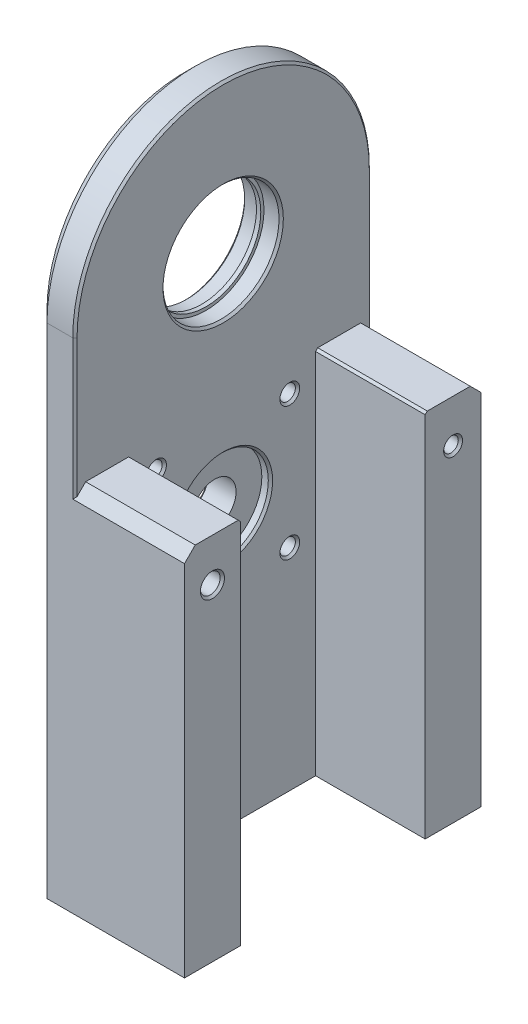
SolidWorks part; units mm, degrees
ref_plane "Ebene vorne" through (0, 0, 0) normal (0, 0, 1) x (1, 0, 0)
ref_plane "Ebene oben" through (0, 0, 0) normal (0, 1, 0) x (1, 0, 0)
ref_plane "Ebene rechts" through (0, 0, 0) normal (1, 0, 0) x (0, 0, -1)
sketch "Sketch2" plane through (0, 0, 0) normal (1, 0, 0) x (0, 0, -1)
  line L1 (0, 0) -> (69, 0)
  line L2 (0, 0) -> (0, 86)
  line L3 (0, 86) -> (69, 86)
  line L4 (69, 0) -> (69, 86)
  line L5 (0, 0) -> (69, 86) construction
  line L6 (0, 86) -> (69, 0) construction
  line L7 (0, 86) -> (69, 86)
  line L8 (0, 86) -> (0, 116)
  line L9 (0, 116) -> (69, 116)
  line L10 (69, 86) -> (69, 116)
  line L11 (0, 86) -> (69, 116) construction
  line L12 (0, 116) -> (69, 86) construction
  circle A0 centre (34.5, 116) radius 34.5
  circle A1 centre (34.5, 116) radius 12.75
  point P4 (34.5, 43)
  point P9 (34.5, 101)
  dimension "D4" = 25.5
  dimension "D1" = 69
  dimension "D2" = 86
  dimension "D3" = 30
extrude "Boss-Extrude1" add sketch "Sketch2" along normal blind 34.5 contours A0 L3 L2 L1 L4 | L7 A0 region at (0, 42.2679, -34.5) region at (0, 84.1895, -34.5)
sketch "Sketch9" plane through (34.5, 0, 0) normal (1, 0, 0) x (0, 0, -1)
  line L0 (13, 86) -> (13, 0)
  line L1 (0, 86) -> (69, 86) construction
  line L2 (0, 0) -> (69, 0) construction
  line L3 (13, 0) -> (56, 0)
  line L4 (56, 0) -> (56, 86)
  line L5 (56, 86) -> (13, 86)
  line L6 (0, 0) -> (0, 86) construction
  line L7 (69, 0) -> (69, 86) construction
  line L9 (13, 0) -> (56, 0)
  line L10 (13, 0) -> (13, 43)
  line L11 (13, 43) -> (56, 43)
  line L12 (56, 0) -> (56, 43)
  line L13 (13, 0) -> (56, 43) construction
  line L14 (13, 43) -> (56, 0) construction
  line L15 (56, 43) -> (13, 43)
  line L16 (56, 43) -> (56, 86)
  line L17 (56, 86) -> (13, 86)
  line L18 (13, 43) -> (13, 86)
  line L19 (56, 43) -> (13, 86) construction
  line L20 (56, 86) -> (13, 43) construction
  circle A0 centre (34.5, 64.5) radius 11
  circle A1 centre (34.5, 64.5) radius 5
  point P15 (34.5, 21.5)
  point P19 (34.5, 64.5)
  line M2 (69, 86) -> (0, 86)
  line M4 (0, 0) -> (69, 0)
  dimension "D3" = 22
  dimension "D4" = 10
  dimension "D1" = 13
  dimension "D2" = 13
extrude "Cut-Extrude1" cut sketch "Sketch9" against normal offset from surface (25.5 mm away) 9 contours L0 L11 L4 A0 M2 | A0 A1 | A1 | L11 L0 L4 M4 region at (34.5, 85.3919, -34.5) region at (34.5, 21.5, -34.5) region at (34.5, 64.5, -23.8111) region at (34.5, 64.5, -34.5) up to face at (0, 43, -34.5)
extrude "Boss-Extrude2" add sketch "Sketch2<5>" along normal up to surface (9 mm away) contours L9 A0 L7 | A0 L8 L3 | A0 L3 L10 | L9 A0 region at (0, 93.069, -4.894) region at (0, 93.069, -64.106) region at (0, 100.9752, -34.5) region at (0, 132.1024, -34.5) up to face at (9, 43, -34.5)
sketch "Sketch2<5>" plane through (0, 0, 0) normal (1, 0, 0) x (0, 0, -1) same geometry as "Sketch2"
extrude "Cut-Extrude2" cut sketch "Sketch9<3>" against normal offset from surface (27.5 mm away) 2 contours A0 A1 | A1 region at (34.5, 64.5, -23.8111) region at (34.5, 64.5, -34.5) up to face at (9, 76.3125, -34.5) offset beyond the face yes
sketch "Sketch9<3>" plane through (34.5, 0, 0) normal (1, 0, 0) x (0, 0, -1) same geometry as "Sketch9"
extrude "Cut-Extrude3" cut sketch "Sketch9<4>" against normal through all contours A1 region at (34.5, 64.5, -34.5)
sketch "Sketch9<4>" plane through (34.5, 0, 0) normal (1, 0, 0) x (0, 0, -1) same geometry as "Sketch9"
sketch "Sketch20" plane through (9, 0, 0) normal (1, 0, 0) x (0, 0, -1)
  circle A0 centre (34.5, 116) radius 13.5
  dimension "D1" = 27
extrude "Cut-Extrude4" cut sketch "Sketch20" against normal blind 4
ref_plane "Plane1" through (4.5, 0, 0) normal (1, 0, 0) x (0, 0, -1)
mirror "Mirror1" about plane through (4.5, 0, 0) normal (1, 0, 0) of "Cut-Extrude4"
hole_wizard "CBORE for M3 Hex Socket Head Cap Screw1" positions "Sketch10" profile "Sketch11" counterbore size "M3" standard "DIN" end condition through all
sketch "Sketch10" plane through (0, 0, 0) normal (-1, 0, 0) x (0, 0, 1)
  line L1 (-50, 49) -> (-19, 49)
  line L2 (-50, 49) -> (-50, 80)
  line L3 (-50, 80) -> (-19, 80)
  line L4 (-19, 49) -> (-19, 80)
  line L5 (-50, 49) -> (-19, 80) construction
  line L6 (-50, 80) -> (-19, 49) construction
  point P1 (-34.5, 64.5)
  point P2 (-19, 80)
  point P5 (-50, 49)
  point P6 (-50, 80)
  point P7 (-19, 49)
  dimension "D1" = 31
sketch "Sketch11" plane through (0, 49, -19) normal (0, 1, 0) x (0, 0, 1)
  line L0 (0, 0) -> (0, 34.5)
  line L1 (0, 34.5) -> (1.8, 34.5)
  line L3 (1.8, 34.5) -> (1.8, 3.4)
  line L4 (1.8, 3.4) -> (3.25, 3.4)
  line L5 (3.25, 3.4) -> (3.25, 0)
  line L7 (3.25, 0) -> (0, 0)
  line L11 (0, -6.35) -> (0, 107.95) construction
  dimension "Thru Hole Dia." = 3.6
  dimension "Thru Hole Depth" = 34.5
  dimension "C'Bore Dia." = 6.5
  dimension "C'Bore Depth" = 3.4
hole_wizard "Ø4.6 (4.6) Diameter Hole1" positions "Sketch12" profile "Sketch13" hole size "Ø4.6" standard "DIN"
sketch "Sketch12" plane through (0, 0, 0) normal (0, -1, 0) x (-1, 0, 0)
  line L0 (-34.5, 69) -> (-34.5, 0) construction
  line L1 (-34.5, 0) -> (-34.5, 13) construction
  line L4 (-64.5, 6.5) -> (-4.5, 6.5)
  line L5 (-64.5, 6.5) -> (-64.5, 62.5)
  line L6 (-64.5, 62.5) -> (-4.5, 62.5)
  line L7 (-4.5, 6.5) -> (-4.5, 62.5)
  line L8 (-64.5, 6.5) -> (-4.5, 62.5) construction
  line L9 (-64.5, 62.5) -> (-4.5, 6.5) construction
  line L10 (-34.5, 69) -> (0, 69) construction
  line L11 (0, 0) -> (0, 69) construction
  point P6 (-34.5, 34.5)
  point P7 (-4.5, 62.5)
  point P12 (-4.5, 6.5)
  point P70 (-4.5, 34.5)
  dimension "D1" = 6.5
  dimension "D2" = 4.5
sketch "Sketch13" plane through (4.5, 0, -34.5) normal (1, 0, 0) x (0, 0, -1)
  line L0 (0, 0) -> (0, 7.382)
  line L1 (0, 7.382) -> (2.3, 6)
  line L2 (2.3, 6) -> (2.3, 0)
  line L5 (2.3, 0) -> (0, 0)
  line L10 (0, 7.382) -> (-2.3, 6) construction
  line L11 (0, -6.35) -> (0, 107.95) construction
  dimension "Hole Dia." = 4.6
  dimension "Hole Depth" = 6
  dimension "Drill Angle" = 118
hole_wizard "CBORE for M3 Hex Socket Head Cap Screw2" positions "Sketch16" profile "Sketch18" counterbore size "M3" standard "DIN" end condition through all
sketch "Sketch16" plane through (0, 0, 0) normal (-1, 0, 0) x (0, 0, 1)
  line L0 (-56, 86) -> (-69, 86) construction
  line L1 (-56, 86) -> (-69, 86)
  line L2 (-62.5, 86) -> (-62.5, 76) construction
  point P4 (-62.5, 76)
  dimension "D1" = 10
sketch "Sketch18" plane through (0, 76, -62.5) normal (0, 1, 0) x (0, 0, 1)
  line L0 (0, 0) -> (0, 34.5)
  line L1 (0, 34.5) -> (1.7, 34.5)
  line L3 (1.7, 34.5) -> (1.7, 3.4)
  line L4 (1.7, 3.4) -> (3.25, 3.4)
  line L5 (3.25, 3.4) -> (3.25, 0)
  line L7 (3.25, 0) -> (0, 0)
  line L11 (0, -6.35) -> (0, 107.95) construction
  dimension "Thru Hole Dia." = 3.4
  dimension "Thru Hole Depth" = 34.5
  dimension "C'Bore Dia." = 6.5
  dimension "C'Bore Depth" = 3.4
hole_wizard "Ø4.6 (4.6) Diameter Hole2" positions "Sketch14" profile "Sketch15" hole size "Ø4.6" standard "DIN"
sketch "Sketch14" plane through (34.5, 0, 0) normal (1, 0, 0) x (0, 0, -1)
  line L0 (6.5, 86) -> (6.5, 76) construction
  line L1 (0, 86) -> (13, 86) construction
  point P2 (6.5, 76)
  dimension "D1" = 10
sketch "Sketch15" plane through (34.5, 76, -6.5) normal (0, 1, 0) x (0, 0, -1)
  line L0 (0, 0) -> (0, 7.382)
  line L1 (0, 7.382) -> (2.3, 6)
  line L2 (2.3, 6) -> (2.3, 0)
  line L5 (2.3, 0) -> (0, 0)
  line L10 (0, 7.382) -> (-2.3, 6) construction
  line L11 (0, -6.35) -> (0, 107.95) construction
  dimension "Hole Dia." = 4.6
  dimension "Hole Depth" = 6
  dimension "Drill Angle" = 118
chamfer "2,5mm Chamfer1" distance 2.5 angle 45 5 edges at (21.75, 86, -69) (21.75, 86, 0) (0, 58, -69) (0, 150.5, -34.5) (0, 58, 0)
chamfer "0,5mm Chamfer2" distance 0.5 angle 45 24 edges at (3.4, 49, -48.2) (9, 49, -51.8) (4.5, 0, -8.8) (4.5, 0, -36.8) (4.5, 0, -64.8) (9, 49, -20.8) (9, 64.5, -45.5) (34.5, 76, -8.8) (9, 80, -51.8) (34.5, 76, -60.8) (9, 80, -20.8) (0, 49, -15.75) (0, 49, -46.75) (0, 64.5, -39.5) (0, 76, -59.25) (0, 80, -46.75) (0, 80, -15.75) (21.75, 86, -13) (9, 99.75, -69) (9, 99.75, 0) (9, 150.5, -34.5) (0, 116, -48) (9, 116, -48) (21.75, 86, -56)
